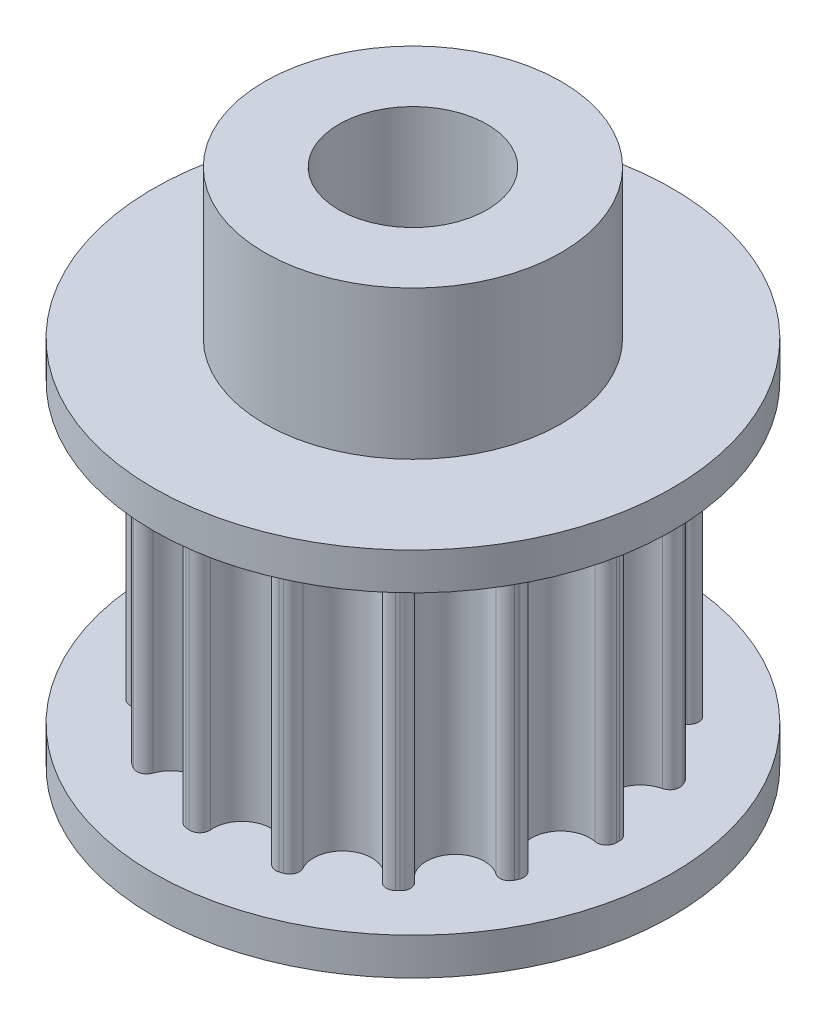
SolidWorks part; units mm, degrees
ref_plane "Front Plane" through (0, 0, 0) normal (0, 0, 1) x (1, 0, 0)
ref_plane "Top Plane" through (0, 0, 0) normal (0, 1, 0) x (1, 0, 0)
ref_plane "Right Plane" through (0, 0, 0) normal (1, 0, 0) x (0, 0, -1)
sketch "Sketch1" plane through (0, 0, 0) normal (0, 1, 0) x (1, 0, 0)
  line L0 (0, 0) -> (11.0666, 0) construction
  line L1 (0, 0) -> (10.8248, 2.3009) construction
  circle A0 centre (0, 0) radius 11.0666 construction
  arc A1 (9.776, 3.6877) -> (10.4307, 0.6074) centre (10.1291, 2.153) ccw
  arc A2 (10.4307, 0.6074) -> (11.0663, 0.0881) centre (10.5329, 0.0838) cw
  arc A3 (11.0663, 0.0881) -> (11.0666, 0) centre (0, 0) cw
  arc A4 (9.776, 3.6877) -> (10.1454, 4.4206) centre (9.6564, 4.2075) ccw
  arc A5 (10.1454, 4.4206) -> (10.1099, 4.5012) centre (0, 0) ccw
  arc A6 (10.1454, -4.4206) -> (10.1099, -4.5012) centre (0, 0) cw
  arc A7 (9.776, -3.6877) -> (10.1454, -4.4206) centre (9.6564, -4.2075) cw
  arc A8 (10.4307, -0.6074) -> (9.776, -3.6877) centre (10.1291, -2.153) ccw
  arc A9 (10.4307, -0.6074) -> (11.0663, -0.0881) centre (10.5329, -0.0838) ccw
  arc A10 (11.0663, -0.0881) -> (11.0666, 0) centre (0, 0) ccw
  arc A11 (7.4702, -8.1649) -> (7.405, -8.2241) centre (0, 0) cw
  arc A12 (7.4309, -7.3451) -> (7.4702, -8.1649) centre (7.1102, -7.7714) cw
  arc A13 (9.2819, -4.7974) -> (7.4309, -7.3451) centre (8.3777, -6.0868) ccw
  arc A14 (9.2819, -4.7974) -> (10.0737, -4.5815) centre (9.5882, -4.3607) ccw
  arc A15 (10.0737, -4.5815) -> (10.1099, -4.5012) centre (0, 0) ccw
  arc A16 (3.5034, -10.4974) -> (3.4198, -10.525) centre (0, 0) cw
  arc A17 (3.8009, -9.7325) -> (3.5034, -10.4974) centre (3.3346, -9.9915) cw
  arc A18 (6.5282, -8.1579) -> (3.8009, -9.7325) centre (5.1777, -8.9681) ccw
  arc A19 (6.5282, -8.1579) -> (7.3393, -8.2828) centre (6.9856, -7.8836) ccw
  arc A20 (7.3393, -8.2828) -> (7.405, -8.2241) centre (0, 0) ccw
  arc A21 (-1.0691, -11.0149) -> (-1.1568, -11.006) centre (0, 0) cw
  arc A22 (-0.4863, -10.4371) -> (-1.0691, -11.0149) centre (-1.0176, -10.484) cw
  arc A23 (2.6456, -10.1079) -> (-0.4863, -10.4371) centre (1.0824, -10.2987) ccw
  arc A24 (2.6456, -10.1079) -> (3.3359, -10.5519) centre (3.1751, -10.0433) ccw
  arc A25 (3.3359, -10.5519) -> (3.4198, -10.525) centre (0, 0) ccw
  arc A26 (-5.4569, -9.6277) -> (-5.5333, -9.584) centre (0, 0) cw
  arc A27 (-4.6894, -9.337) -> (-5.4569, -9.6277) centre (-5.1938, -9.1637) cw
  arc A28 (-1.6943, -10.3101) -> (-4.6894, -9.337) centre (-3.2, -9.8486) ccw
  arc A29 (-1.6943, -10.3101) -> (-1.2443, -10.9964) centre (-1.1844, -10.4664) ccw
  arc A30 (-1.2443, -10.9964) -> (-1.1568, -11.006) centre (0, 0) ccw
  arc A31 (-8.901, -6.5759) -> (-8.9531, -6.5048) centre (0, 0) cw
  arc A32 (-8.0816, -6.6224) -> (-8.901, -6.5759) centre (-8.472, -6.2589) cw
  arc A33 (-5.7414, -8.7296) -> (-8.0816, -6.6224) centre (-6.9291, -7.6956) ccw
  arc A34 (-5.7414, -8.7296) -> (-5.6094, -9.5396) centre (-5.339, -9.0798) ccw
  arc A35 (-5.6094, -9.5396) -> (-5.5333, -9.584) centre (0, 0) ccw
  arc A36 (-10.8061, -2.387) -> (-10.8248, -2.3009) centre (0, 0) cw
  arc A37 (-10.0765, -2.7628) -> (-10.8061, -2.387) centre (-10.2853, -2.2719) cw
  arc A38 (-8.7956, -5.6397) -> (-10.0765, -2.7628) centre (-9.4601, -4.2119) ccw
  arc A39 (-8.7956, -5.6397) -> (-9.0046, -6.4333) centre (-8.5706, -6.1232) ccw
  arc A40 (-9.0046, -6.4333) -> (-8.9531, -6.5048) centre (0, 0) ccw
  arc A41 (-10.8428, 2.2146) -> (-10.8248, 2.3009) centre (0, 0) cw
  arc A42 (-10.3291, 1.5746) -> (-10.8428, 2.2146) centre (-10.3201, 2.1079) cw
  arc A43 (-10.3291, -1.5746) -> (-10.3291, 1.5746) centre (-10.3554, 0) ccw
  arc A44 (-10.3291, -1.5746) -> (-10.8428, -2.2146) centre (-10.3201, -2.1079) ccw
  arc A45 (-10.8428, -2.2146) -> (-10.8248, -2.3009) centre (0, 0) ccw
  arc A46 (-9.0046, 6.4333) -> (-8.9531, 6.5048) centre (0, 0) cw
  arc A47 (-8.7956, 5.6397) -> (-9.0046, 6.4333) centre (-8.5706, 6.1232) cw
  arc A48 (-10.0765, 2.7628) -> (-8.7956, 5.6397) centre (-9.4601, 4.2119) ccw
  arc A49 (-10.0765, 2.7628) -> (-10.8061, 2.387) centre (-10.2853, 2.2719) ccw
  arc A50 (-10.8061, 2.387) -> (-10.8248, 2.3009) centre (0, 0) ccw
  arc A51 (-5.6094, 9.5396) -> (-5.5333, 9.584) centre (0, 0) cw
  arc A52 (-5.7414, 8.7296) -> (-5.6094, 9.5396) centre (-5.339, 9.0798) cw
  arc A53 (-8.0816, 6.6224) -> (-5.7414, 8.7296) centre (-6.9291, 7.6956) ccw
  arc A54 (-8.0816, 6.6224) -> (-8.901, 6.5759) centre (-8.472, 6.2589) ccw
  arc A55 (-8.901, 6.5759) -> (-8.9531, 6.5048) centre (0, 0) ccw
  arc A56 (-1.2443, 10.9964) -> (-1.1568, 11.006) centre (0, 0) cw
  arc A57 (-1.6943, 10.3101) -> (-1.2443, 10.9964) centre (-1.1844, 10.4664) cw
  arc A58 (-4.6894, 9.337) -> (-1.6943, 10.3101) centre (-3.2, 9.8486) ccw
  arc A59 (-4.6894, 9.337) -> (-5.4569, 9.6277) centre (-5.1938, 9.1637) ccw
  arc A60 (-5.4569, 9.6277) -> (-5.5333, 9.584) centre (0, 0) ccw
  arc A61 (3.3359, 10.5519) -> (3.4198, 10.525) centre (0, 0) cw
  arc A62 (2.6456, 10.1079) -> (3.3359, 10.5519) centre (3.1751, 10.0433) cw
  arc A63 (-0.4863, 10.4371) -> (2.6456, 10.1079) centre (1.0824, 10.2987) ccw
  arc A64 (-0.4863, 10.4371) -> (-1.0691, 11.0149) centre (-1.0176, 10.484) ccw
  arc A65 (-1.0691, 11.0149) -> (-1.1568, 11.006) centre (0, 0) ccw
  arc A66 (7.3393, 8.2828) -> (7.405, 8.2241) centre (0, 0) cw
  arc A67 (6.5282, 8.1579) -> (7.3393, 8.2828) centre (6.9856, 7.8836) cw
  arc A68 (3.8009, 9.7325) -> (6.5282, 8.1579) centre (5.1777, 8.9681) ccw
  arc A69 (3.8009, 9.7325) -> (3.5034, 10.4974) centre (3.3346, 9.9915) ccw
  arc A70 (3.5034, 10.4974) -> (3.4198, 10.525) centre (0, 0) ccw
  arc A71 (10.0737, 4.5815) -> (10.1099, 4.5012) centre (0, 0) cw
  arc A72 (9.2819, 4.7974) -> (10.0737, 4.5815) centre (9.5882, 4.3607) cw
  arc A73 (7.4309, 7.3451) -> (9.2819, 4.7974) centre (8.3777, 6.0868) ccw
  arc A74 (7.4309, 7.3451) -> (7.4702, 8.1649) centre (7.1102, 7.7714) ccw
  arc A75 (7.4702, 8.1649) -> (7.405, 8.2241) centre (0, 0) ccw
  circle A76 centre (0, 0) radius 4
  point P23 (8.5887, 1.8256)
  point P44 (0, 0)
  dimension "D1" = 22.1332
  dimension "D3" = 1.5748
  dimension "D4" = 0.5334
  dimension "D7" = 8
  dimension "D2" = 12
  dimension "D5" = 2.286
  dimension "D6" = 15
extrude "Boss-Extrude1" add sketch "Sketch1" along normal mid plane 16 contours A71 A72 A73 A74 A75 A66 A67 A68 A69 A70 A61 A62 A63 A64 A65 A56 A57 A58 A59 A60 A51 A52 A53 A54 A55 A46 A47 A48 A49 A50 A41 A42 A43 A44 A45 A36 A37 A38 A39 A40 A31 A32 A33 A34 A35 A26 A27 A28 A29 region at (8.2847, 0, -1.761)
sketch "Sketch2" plane through (0, 8, 0) normal (0, 1, 0) x (1, 0, 0)
  circle A0 centre (0, 0) radius 4 construction
  circle A1 centre (0, 0) radius 4
  circle A2 centre (0, 0) radius 8
  circle A3 centre (0, 0) radius 14
  dimension "D1" = 16
  dimension "D2" = 28
extrude "Boss-Extrude2" add sketch "Sketch2" along normal blind 10 contours A2 A1 region at (-7.7737, 8, 0)
extrude "Boss-Extrude3" add sketch "Sketch2<3>" along normal blind 2 contours A3 A2 | A2 A1 region at (-7.7737, 8, 0) region at (-13.604, 8, 0)
sketch "Sketch2<3>" plane through (0, 8, 0) normal (0, 1, 0) x (1, 0, 0) same geometry as "Sketch2"
mirror "Mirror1" about plane through (0, 0, 0) normal (0, 1, 0) of "Boss-Extrude3"
sketch "Sketch3" plane through (0, -8, 0) normal (0, 1, 0) x (1, 0, 0)
  circle A0 centre (0, 0) radius 12.8066 construction
  dimension "D1" = 25.6132
equation "\"T\"= 15"
equation "\"P\"= 5mm"
equation "\"TanD\"= \"PD\" - \"BeltWidth\""
equation "\"Angle\"= 360 / \"T\""
equation "\"D1@Sketch1\"=\"TanD\""
equation "\"D2@Sketch1\"=\"Angle\"/2"
equation "\"D6@Sketch1\"=\"T\""
equation "\"W\"= 16mm"
equation "\"D1@Boss-Extrude1\"=\"W\""
equation "\"TolRatio\"= 32 / 33"
equation "\"BeltWidth\"= 1.74mm"
equation "\"PD\"= \"T\" * \"P\" / PI"
equation "\"D1@Sketch3\"=\"PD\" + \"BeltWidth\""
